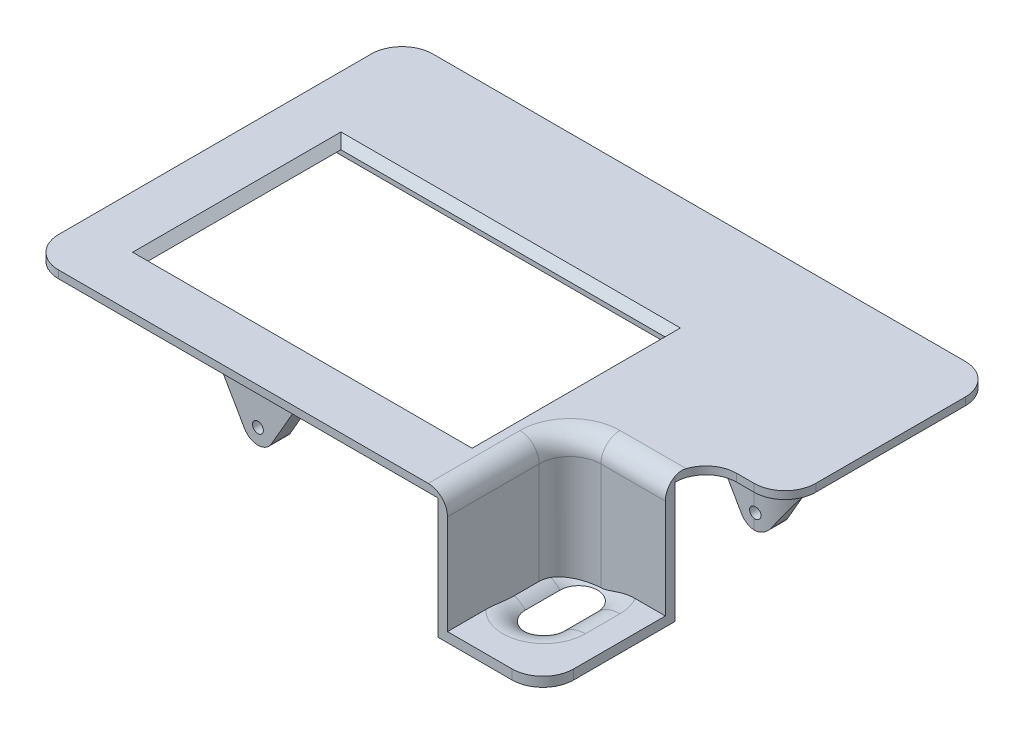
SolidWorks part; units mm, degrees
ref_plane "Front Plane" through (0, 0, 0) normal (0, 0, 1) x (1, 0, 0)
ref_plane "Top Plane" through (0, 0, 0) normal (0, 1, 0) x (1, 0, 0)
ref_plane "Right Plane" through (0, 0, 0) normal (1, 0, 0) x (0, 0, -1)
sketch "Sketch1" plane through (0, 0, 0) normal (0, 1, 0) x (1, 0, 0)
  line L0 (-77, 40.5) -> (-77, -40.5)
  line L1 (-69, -48.5) -> (29.28, -48.5)
  line L2 (29.28, -48.5) -> (29.28, -46)
  line L3 (29.28, -46) -> (-66.5, -46) construction
  line L4 (-74.5, -38) -> (-74.5, 38) construction
  line L5 (-66.5, 46) -> (66.5, 46) construction
  line L6 (74.5, 38) -> (74.5, 4.25) construction
  line L7 (66.5, -3.75) -> (62, -3.75) construction
  line L8 (54, -11.75) -> (54, -14.25) construction
  line L9 (54, -14.25) -> (56.5, -14.25)
  line L10 (64.5, -6.25) -> (69, -6.25)
  line L11 (77, 1.75) -> (77, 40.5)
  line L12 (69, 48.5) -> (-69, 48.5)
  line L13 (29.28, -46) -> (29.28, -14.25)
  line L14 (29.28, -14.25) -> (54, -14.25)
  arc A0 (-77, -40.5) -> (-69, -48.5) centre (-69, -40.5) ccw
  arc A1 (-74.5, -38) -> (-66.5, -46) centre (-66.5, -38) ccw construction
  arc A2 (-66.5, 46) -> (-74.5, 38) centre (-66.5, 38) ccw construction
  arc A3 (74.5, 38) -> (66.5, 46) centre (66.5, 38) ccw construction
  arc A4 (66.5, -3.75) -> (74.5, 4.25) centre (66.5, 4.25) ccw construction
  arc A5 (62, -3.75) -> (54, -11.75) centre (62, -11.75) ccw construction
  arc A6 (64.5, -6.25) -> (56.5, -14.25) centre (64.5, -14.25) ccw
  arc A7 (69, -6.25) -> (77, 1.75) centre (69, 1.75) ccw
  arc A8 (77, 40.5) -> (69, 48.5) centre (69, 40.5) ccw
  arc A9 (-69, 48.5) -> (-77, 40.5) centre (-69, 40.5) ccw
extrude "Boss-Extrude1" add sketch "Sketch1" along normal blind 2
sketch "Sketch2" plane through (0, 0, 0) normal (0, -1, 0) x (1, 0, 0)
  line L0 (54, 11.75) -> (54, 14.25) construction
  line L1 (66.5, 3.75) -> (62, 3.75) construction
  line L2 (74.5, -38) -> (74.5, -4.25) construction
  line L3 (-66.5, -46) -> (66.5, -46) construction
  line L4 (-74.5, 38) -> (-74.5, -38) construction
  line L5 (29.28, 46) -> (-66.5, 46) construction
  line L6 (54, 11.75) -> (54, 14.25)
  line L21 (66.5, 3.75) -> (62, 3.75)
  line L22 (74.5, -38) -> (74.5, -4.25)
  line L23 (-66.5, -46) -> (66.5, -46)
  line L24 (-74.5, 38) -> (-74.5, -38)
  line L25 (29.28, 46) -> (-66.5, 46)
  line L26 (29.28, 44) -> (-66.5, 44)
  line L27 (-72.5, 38) -> (-72.5, -38)
  line L28 (-66.5, -44) -> (66.5, -44)
  line L29 (72.5, -38) -> (72.5, -4.25)
  line L30 (66.5, 1.75) -> (62, 1.75)
  line L31 (52, 11.75) -> (52, 14.25)
  line L32 (29.28, 46) -> (29.28, 44)
  line L33 (54, 14.25) -> (52, 14.25)
  arc A0 (-74.5, -38) -> (-66.5, -46) centre (-66.5, -38) ccw construction
  arc A1 (54, 11.75) -> (62, 3.75) centre (62, 11.75) ccw construction
  arc A2 (74.5, -4.25) -> (66.5, 3.75) centre (66.5, -4.25) ccw construction
  arc A3 (66.5, -46) -> (74.5, -38) centre (66.5, -38) ccw construction
  arc A4 (-66.5, 46) -> (-74.5, 38) centre (-66.5, 38) ccw construction
  arc A15 (-74.5, -38) -> (-66.5, -46) centre (-66.5, -38) ccw
  arc A16 (54, 11.75) -> (62, 3.75) centre (62, 11.75) ccw
  arc A17 (74.5, -4.25) -> (66.5, 3.75) centre (66.5, -4.25) ccw
  arc A18 (66.5, -46) -> (74.5, -38) centre (66.5, -38) ccw
  arc A19 (-66.5, 46) -> (-74.5, 38) centre (-66.5, 38) ccw
  arc A20 (-66.5, 44) -> (-72.5, 38) centre (-66.5, 38) ccw
  arc A21 (-72.5, -38) -> (-66.5, -44) centre (-66.5, -38) ccw
  arc A22 (66.5, -44) -> (72.5, -38) centre (66.5, -38) ccw
  arc A23 (72.5, -4.25) -> (66.5, 1.75) centre (66.5, -4.25) ccw
  arc A24 (52, 11.75) -> (62, 1.75) centre (62, 11.75) ccw
  dimension "D1" = 2
extrude "Boss-Extrude2" add sketch "Sketch2" along normal blind 2
sketch "Sketch3" plane through (0, 0, 14.25) normal (0, 0, 1) x (1, 0, 0)
  line L0 (29.28, 2) -> (29.28, 0) construction
  line L5 (56.5, 2) -> (29.28, 2)
  line L6 (56.5, 2) -> (56.5, -31.28)
  line L7 (56.5, -31.28) -> (29.28, -31.28)
  line L8 (29.28, 2) -> (29.28, -31.28)
  dimension "D1" = 33.28
extrude "Boss-Extrude3" add sketch "Sketch3" along normal blind 2.5
sketch "Sketch4" plane through (29.28, 0, 0) normal (1, 0, 0) x (0, 0, -1)
  line L1 (-48.5, 2) -> (-16.75, 2)
  line L2 (-48.5, 2) -> (-48.5, -31.28)
  line L3 (-48.5, -31.28) -> (-16.75, -31.28)
  line L4 (-16.75, 2) -> (-16.75, -31.28)
extrude "Boss-Extrude4" add sketch "Sketch4" along normal blind 2.5
sketch "Sketch5" plane through (0, -31.28, 0) normal (0, -1, 0) x (1, 0, 0)
  line L0 (-69, 48.5) -> (29.28, 48.5) construction
  line L1 (29.28, 14.25) -> (56.5, 14.25)
  line L2 (29.28, 14.25) -> (29.28, 48.5)
  line L3 (29.28, 48.5) -> (56.5, 48.5)
  line L4 (56.5, 14.25) -> (56.5, 48.5)
  line L5 (56.5, 16.75) -> (56.5, 14.25) construction
extrude "Boss-Extrude5" add sketch "Sketch5" against normal blind 2.5
fillet "Fillet1" radius 8 1 edges at (56.5, -30.03, 48.5)
sketch "Sketch6" plane through (0, -28.78, 0) normal (0, 1, 0) x (1, 0, 0)
  line L0 (39.43, -22.12) -> (39.43, -31.12) construction
  line L1 (44.31, -22.12) -> (44.31, -31.12)
  line L2 (34.55, -22.12) -> (34.55, -31.12)
  line L3 (56.5, -16.75) -> (56.5, -40.5) construction
  line L4 (48.5, -48.5) -> (31.78, -48.5) construction
  arc A0 (44.31, -22.12) -> (34.55, -22.12) centre (39.43, -22.12) ccw
  arc A1 (34.55, -31.12) -> (44.31, -31.12) centre (39.43, -31.12) ccw
  point P2 (39.43, -26.62)
  dimension "D2" = 4.88
  dimension "D1" = 9
  dimension "D3" = 21.95
  dimension "D4" = 26.38
extrude "Cut-Extrude1" cut sketch "Sketch6" against normal up to next
fillet "Fillet3" radius 8 2 edges at (29.28, -15.64, 14.25) (31.78, -13.39, 16.75)
fillet "Fillet4" radius 8 3 edges at (39.43, -28.78, 36) (39.43, -28.78, 17.24) (44.31, -28.78, 26.62)
fillet "Fillet6" radius 5 3 edges at (31.78, 2, 36.625) (34.1231, 2, 19.0931) (48.14, 2, 16.75)
sketch "Sketch7" plane through (0, 0, 0) normal (0, -1, 0) x (1, 0, 0)
  line L0 (-77, -40.5) -> (-77, 40.5) construction
  line L1 (27.38, -21.88) -> (-69.62, -21.88)
  line L2 (27.38, -21.88) -> (27.38, 36.92)
  line L3 (27.38, 36.92) -> (-69.62, 36.92)
  line L4 (-69.62, -21.88) -> (-69.62, 36.92)
  line L5 (27.38, -21.88) -> (-69.62, 36.92) construction
  line L6 (27.38, 36.92) -> (-69.62, -21.88) construction
  line L7 (-69, 48.5) -> (29.28, 48.5) construction
  line L8 (-71.62, -23.88) -> (-71.62, 38.92)
  line L9 (29.38, 38.92) -> (-71.62, 38.92)
  line L10 (29.38, -23.88) -> (29.38, 38.92)
  line L11 (29.38, -23.88) -> (-71.62, -23.88)
  point P0 (-21.12, 7.52)
  dimension "D1" = 97
  dimension "D2" = 58.8
  dimension "D3" = 7.38
  dimension "D4" = 11.58
  dimension "D5" = 2
extrude "Boss-Extrude6" add sketch "Sketch7" along normal blind 6
sketch "Sketch8" plane through (0, 2, 0) normal (0, 1, 0) x (1, 0, 0)
  line L0 (-69, -48.5) -> (29.28, -48.5) construction
  line L1 (-61.42, 17.08) -> (22.58, 17.08)
  line L2 (-61.42, 17.08) -> (-61.42, -32.92)
  line L3 (-61.42, -32.92) -> (22.58, -32.92)
  line L4 (22.58, 17.08) -> (22.58, -32.92)
  line L5 (-61.42, 17.08) -> (22.58, -32.92) construction
  line L6 (-61.42, -32.92) -> (22.58, 17.08) construction
  line L7 (-77, 40.5) -> (-77, -40.5) construction
  point P0 (-19.42, -7.92)
  dimension "D1" = 50
  dimension "D2" = 84
  dimension "D3" = 15.58
  dimension "D4" = 15.58
extrude "Cut-Extrude2" cut sketch "Sketch8" against normal up to next
chamfer "Chamfer1" distance 2 angle 45 4 edges at (-19.42, 2, 32.92) (-61.42, 2, 7.92) (-19.42, 2, -17.08) (22.58, 2, 7.92)
sketch "Sketch9" plane through (0, 0, 48.5) normal (0, 0, 1) x (1, 0, 0)
  line L0 (-77, 2) -> (-77, 0) construction
  line L1 (-23.3241, -12) -> (-30.2523, 0)
  line L2 (-30.2523, 0) -> (-9.4677, 0)
  line L3 (69, 0) -> (-69, 0) construction
  line L4 (-9.4677, 0) -> (-16.3959, -12)
  circle A0 centre (-19.86, -10) radius 1.4
  arc A1 (-23.3241, -12) -> (-16.3959, -12) centre (-19.86, -10) ccw
  dimension "D1" = 2.8
  dimension "D2" = 8
  dimension "D3" = 57.14
  dimension "D4" = 10
  dimension "D5" = 60
extrude "Boss-Extrude7" add sketch "Sketch9" against normal blind 5 from surface starting at face at (-18.61, -1, 46)
sketch "Sketch10" plane through (0, 0, 0) normal (0, 0, 1) x (1, 0, 0)
  line L1 (77, 0) -> (69, 0) construction
  line L2 (77, 2) -> (77, 0) construction
  line L3 (70.2141, -9) -> (75.4103, 0)
  line L4 (75.4103, 0) -> (58.0897, 0)
  line L5 (69, 0) -> (-69, 0) construction
  line L6 (58.0897, 0) -> (63.2859, -9)
  arc A0 (63.2859, -9) -> (70.2141, -9) centre (66.75, -7) ccw
  circle A1 centre (66.75, -7) radius 1.4
  dimension "D1" = 2.8
  dimension "D2" = 8
  dimension "D3" = 10.25
  dimension "D4" = 7
  dimension "D5" = 60
extrude "Boss-Extrude8" add sketch "Sketch10" against normal blind 5 from surface starting at face at (64.25, -1, 3.75)
sketch "Sketch11" plane through (0, 0, -46) normal (0, 0, -1) x (-1, 0, 0)
  line L0 (-69, 0) -> (69, 0) construction
  line L1 (77, 2) -> (77, 0) construction
  line L2 (-77, 2) -> (-77, 0) construction
  line L3 (-65.4641, -9) -> (-70.6603, 0)
  line L5 (-70.6603, 0) -> (-53.3397, 0)
  line L6 (-53.3397, 0) -> (-58.5359, -9)
  line L7 (-69, 0) -> (-77, 0) construction
  line L8 (58.5359, -9) -> (53.3397, 0)
  line L12 (70.6603, 0) -> (65.4641, -9)
  line L13 (77, 0) -> (69, 0) construction
  line L14 (53.3397, 0) -> (70.6603, 0)
  circle A0 centre (-62, -7) radius 1.4
  circle A1 centre (62, -7) radius 1.4
  arc A2 (-65.4641, -9) -> (-58.5359, -9) centre (-62, -7) ccw
  arc A3 (58.5359, -9) -> (65.4641, -9) centre (62, -7) ccw
  dimension "D4" = 2.8
  dimension "D5" = 8
  dimension "D1" = 7
  dimension "D2" = 15
  dimension "D3" = 15
  dimension "D6" = 60
  dimension "D7" = 60
extrude "Boss-Extrude9" add sketch "Sketch11" against normal blind 5
sketch "Sketch12" plane through (0, 0, 0) normal (0, -1, 0) x (1, 0, 0)
  line L0 (-66.5, -46) -> (66.5, -46) construction
  line L1 (66.5, 3.75) -> (62, 3.75) construction
  line L2 (-66.5, -46) -> (66.5, -46)
  line L3 (66.5, 3.75) -> (62, 3.75)
  line L4 (54, 11.75) -> (84.2957, 11.75)
  line L5 (84.2957, 11.75) -> (84.2957, -4.25)
  line L6 (84.2957, -4.25) -> (74.5, -4.25)
  line L7 (74.5, -38) -> (84.2957, -38)
  line L8 (84.2957, -38) -> (84.2957, -62.9296)
  line L9 (84.2957, -62.9296) -> (-82.1257, -61.468)
  line L10 (-82.1257, -61.468) -> (-82.1257, -38)
  line L11 (-82.1257, -38) -> (-74.5, -38)
  arc A0 (66.5, -46) -> (74.5, -38) centre (66.5, -38) ccw construction
  arc A1 (-74.5, -38) -> (-66.5, -46) centre (-66.5, -38) ccw construction
  arc A2 (54, 11.75) -> (62, 3.75) centre (62, 11.75) ccw construction
  arc A3 (74.5, -4.25) -> (66.5, 3.75) centre (66.5, -4.25) ccw construction
  arc A4 (66.5, -46) -> (74.5, -38) centre (66.5, -38) ccw
  arc A5 (-74.5, -38) -> (-66.5, -46) centre (-66.5, -38) ccw
  arc A6 (54, 11.75) -> (62, 3.75) centre (62, 11.75) ccw
  arc A7 (74.5, -4.25) -> (66.5, 3.75) centre (66.5, -4.25) ccw
extrude "Cut-Extrude3" cut sketch "Sketch12" along normal through all
